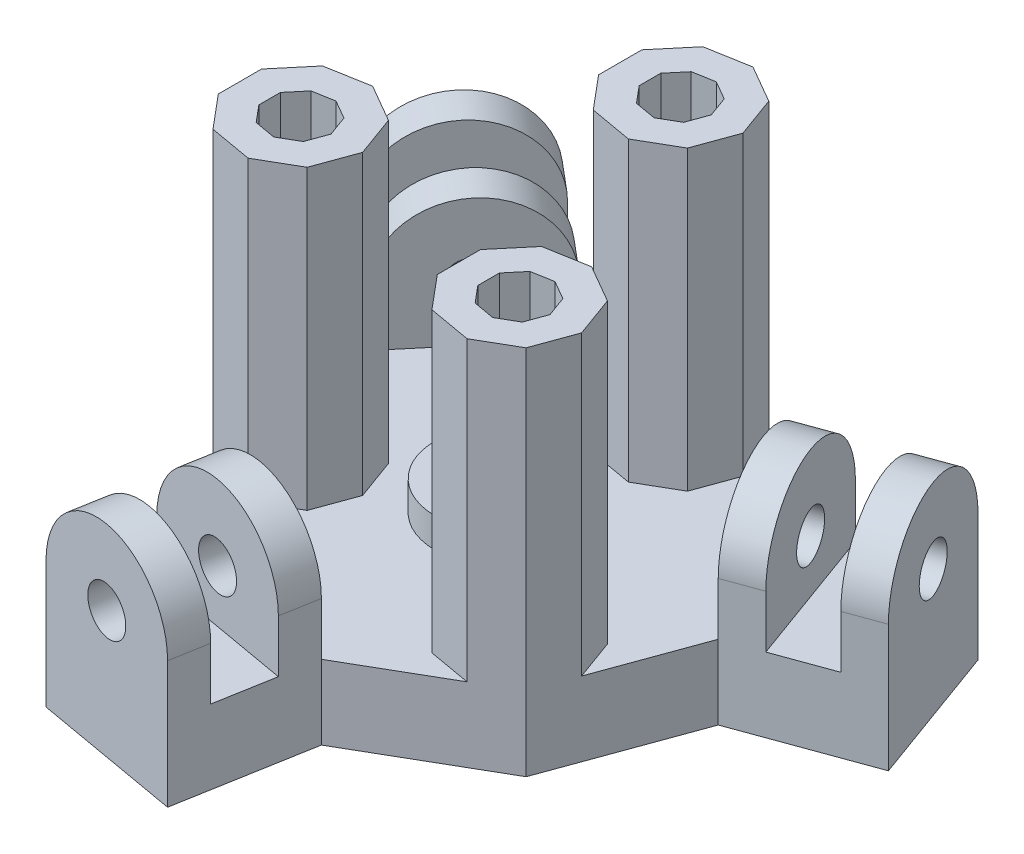
SolidWorks part; units mm, degrees
ref_plane "Front Plane" through (0, 0, 0) normal (0, 0, 1) x (1, 0, 0)
ref_plane "Top Plane" through (0, 0, 0) normal (0, 1, 0) x (1, 0, 0)
ref_plane "Right Plane" through (0, 0, 0) normal (1, 0, 0) x (0, 0, -1)
sketch "Sketch1" plane through (0, 0, 0) normal (0, 1, 0) x (1, 0, 0)
  line L0 (-17.5976, -6.405) -> (-9.3635, -16.2181)
  line L1 (14.3457, -12.0375) -> (18.727, 0)
  line L2 (18.727, 0) -> (14.3457, 12.0375)
  line L3 (14.3457, 12.0375) -> (3.2519, 18.4425)
  line L4 (3.2519, 18.4425) -> (-9.3635, 16.2181)
  line L5 (-9.3635, 16.2181) -> (-17.5976, 6.405)
  line L6 (-17.5976, 6.405) -> (-17.5976, -6.405)
  line L7 (-9.3635, -16.2181) -> (3.2519, -18.4425)
  line L8 (3.2519, -18.4425) -> (14.3457, -12.0375)
  line L9 (14.3457, 12.0375) -> (18.727, 0)
  line L10 (14.3457, 12.0375) -> (25.0112, 15.9194)
  line L11 (18.727, 0) -> (29.3925, 3.8819)
  line L12 (25.0112, 15.9194) -> (29.3925, 3.8819)
  line L13 (3.2519, -18.4425) -> (-9.3635, -16.2181)
  line L14 (3.2519, -18.4425) -> (1.281, -29.6201)
  line L15 (-9.3635, -16.2181) -> (-11.3344, -27.3956)
  line L16 (1.281, -29.6201) -> (-11.3344, -27.3956)
  line L17 (-17.5976, 6.405) -> (-9.3635, 16.2181)
  line L18 (-17.5976, 6.405) -> (-26.2922, 13.7007)
  line L19 (-9.3635, 16.2181) -> (-18.0581, 23.5137)
  line L20 (-26.2922, 13.7007) -> (-18.0581, 23.5137)
  circle A0 centre (0, 0) radius 17.5976 construction
  circle A1 centre (0, 0) radius 4
  dimension "D1" = 35.1953
  dimension "D2" = 8
  dimension "D3" = 11.35
extrude "Boss-Extrude1" add sketch "Sketch1" along normal blind 6.35 contours L16 L14 L7 L15 | L7 L8 L1 L2 L3 L4 L5 L6 L0 A1 | L12 L10 L2 L11 | L20 L18 L5 L19 region at (-17.08, 0, 0) region at (-4.0413, 0, 22.9191) region at (-17.8279, 0, -14.9594) region at (21.8691, 0, -7.9597)
ref_plane "Plane1" through (-5.0267, 0, 28.5079) normal (0.1736, 0, -0.9848) x (-0.9848, 0, -0.1736)
sketch "Sketch4" plane through (-5.0267, 0, 28.5079) normal (0.1736, 0, -0.9848) x (-0.9848, 0, -0.1736)
  line L0 (-6.405, 6.35) -> (-6.405, 10.85)
  line L1 (6.405, 6.35) -> (6.405, 10.85)
  line L2 (-6.405, 6.35) -> (6.405, 6.35)
  arc A0 (6.405, 10.85) -> (-6.405, 10.85) centre (0, 10.85) ccw
  circle A1 centre (0, 10.85) radius 2
  dimension "D2" = 4
  dimension "D1" = 4.5
extrude "Boss-Extrude2" add sketch "Sketch4" along normal blind 3.18
ref_plane "Plane2" through (-3.0558, 0, 17.3303) normal (0.1736, 0, -0.9848) x (-0.9848, 0, -0.1736)
sketch "Sketch6" plane through (-3.0558, 0, 17.3303) normal (0.1736, 0, -0.9848) x (-0.9848, 0, -0.1736)
  line L0 (-6.405, 6.35) -> (-6.405, 10.85)
  line L1 (6.405, 6.35) -> (6.405, 10.85)
  line L2 (-6.405, 6.35) -> (6.405, 6.35)
  arc A0 (6.405, 10.85) -> (-6.405, 10.85) centre (0, 10.85) ccw
  circle A1 centre (0, 10.85) radius 2
  dimension "D2" = 4
  dimension "D1" = 4.5
extrude "Boss-Extrude4" add sketch "Sketch6" against normal blind 3.175
ref_plane "Plane3" through (27.2019, 0, -9.9007) normal (-0.9397, 0, 0.342) x (0.342, 0, 0.9397)
sketch "Sketch8" plane through (27.2019, 0, -9.9007) normal (-0.9397, 0, 0.342) x (0.342, 0, 0.9397)
  line L0 (-6.405, 10.85) -> (-6.405, 6.35)
  line L1 (-6.405, 6.35) -> (6.405, 6.35)
  line L2 (6.405, 6.35) -> (6.405, 10.85)
  arc A0 (6.405, 10.85) -> (-6.405, 10.85) centre (0, 10.85) ccw
  circle A1 centre (0, 10.85) radius 2
  dimension "D2" = 4
  dimension "D1" = 4.5
extrude "Boss-Extrude5" add sketch "Sketch8" along normal blind 3.175
ref_plane "Plane4" through (16.5364, 0, -6.0187) normal (-0.9397, 0, 0.342) x (0.342, 0, 0.9397)
sketch "Sketch9" plane through (16.5364, 0, -6.0187) normal (-0.9397, 0, 0.342) x (0.342, 0, 0.9397)
  line L0 (-6.405, 6.35) -> (-6.405, 10.85)
  line L1 (-6.405, 6.35) -> (6.405, 6.35)
  line L2 (6.405, 6.35) -> (6.405, 10.85)
  arc A0 (-6.405, 10.85) -> (6.405, 10.85) centre (0, 10.85) cw
  circle A1 centre (0, 10.85) radius 2
  dimension "D2" = 4
  dimension "D1" = 4.5
extrude "Boss-Extrude6" add sketch "Sketch9" against normal blind 3.175
ref_plane "Plane5" through (-22.1752, 0, -18.6072) normal (0.766, 0, 0.6428) x (0.6428, 0, -0.766)
sketch "Sketch10" plane through (-22.1752, 0, -18.6072) normal (0.766, 0, 0.6428) x (0.6428, 0, -0.766)
  line L0 (-6.405, 10.85) -> (-6.405, 6.35)
  line L1 (-6.405, 6.35) -> (6.405, 6.35)
  line L2 (6.405, 6.35) -> (6.405, 10.85)
  arc A0 (6.405, 10.85) -> (-6.405, 10.85) centre (0, 10.85) ccw
  circle A1 centre (0, 10.85) radius 2
  dimension "D2" = 4
  dimension "D1" = 4.5
extrude "Boss-Extrude7" add sketch "Sketch10" along normal blind 3.175
ref_plane "Plane6" through (-13.4806, 0, -11.3115) normal (0.766, 0, 0.6428) x (0.6428, 0, -0.766)
sketch "Sketch11" plane through (-13.4806, 0, -11.3115) normal (0.766, 0, 0.6428) x (0.6428, 0, -0.766)
  line L0 (-6.405, 10.85) -> (-6.405, 6.35)
  line L1 (-6.405, 6.35) -> (6.405, 6.35)
  line L2 (6.405, 6.35) -> (6.405, 10.85)
  arc A0 (6.405, 10.85) -> (-6.405, 10.85) centre (0, 10.85) ccw
  circle A1 centre (0, 10.85) radius 2
  dimension "D2" = 4
  dimension "D1" = 4.5
extrude "Boss-Extrude8" add sketch "Sketch11" against normal blind 3.175
ref_plane "Plane7" through (0, 6.35, 0) normal (0, 1, 0) x (1, 0, 0)
sketch "Sketch12" plane through (0, 6.35, 0) normal (0, 1, 0) x (1, 0, 0)
  line L9 (14.3457, -12.0375) -> (18.727, 0) construction
  line L29 (14.3457, -12.0375) -> (15.6105, -8.5626)
  line L38 (15.6105, -8.5626) -> (14.3457, -5.0876)
  line L48 (6.4544, 9.6437) -> (7.7192, 13.1186)
  line L49 (3.2519, 18.4425) -> (-0.3898, 17.8004)
  line L50 (-0.3898, 17.8004) -> (-2.7668, 14.9676)
  line L51 (-2.7668, 14.9676) -> (-2.7668, 11.2696)
  line L52 (-2.7668, 11.2696) -> (-0.3898, 8.4369)
  line L53 (-0.3898, 8.4369) -> (3.2519, 7.7947)
  line L54 (3.2519, 7.7947) -> (6.4544, 9.6437)
  line L55 (7.7192, 13.1186) -> (6.4544, 16.5935)
  line L56 (6.4544, 16.5935) -> (3.2519, 18.4425)
  line L57 (14.3457, -5.0876) -> (11.1432, -3.2387)
  line L58 (11.1432, -3.2387) -> (7.5015, -3.8808)
  line L59 (7.5015, -3.8808) -> (5.1245, -6.7136)
  line L60 (5.1245, -6.7136) -> (5.1245, -10.4115)
  line L61 (5.1245, -10.4115) -> (7.5015, -13.2443)
  line L62 (7.5015, -13.2443) -> (11.1432, -13.8865)
  line L63 (11.1432, -13.8865) -> (14.3457, -12.0375)
  line L64 (-17.5976, -6.405) -> (-9.3635, -16.2181) construction
  line L65 (3.2519, -18.4425) -> (14.3457, -12.0375) construction
  line L66 (-17.5976, -6.405) -> (-15.2206, -9.2378)
  line L67 (-15.2206, -9.2378) -> (-11.5789, -9.8799)
  line L68 (-11.5789, -9.8799) -> (-8.3764, -8.031)
  line L69 (-8.3764, -8.031) -> (-7.1116, -4.556)
  line L70 (-7.1116, -4.556) -> (-8.3764, -1.0811)
  line L71 (-8.3764, -1.0811) -> (-11.5789, 0.7678)
  line L72 (-11.5789, 0.7678) -> (-15.2206, 0.1257)
  line L73 (-15.2206, 0.1257) -> (-17.5976, -2.7071)
  line L74 (-17.5976, -2.7071) -> (-17.5976, -6.405)
  line L75 (14.3457, 12.0375) -> (3.2519, 18.4425) construction
  line L76 (-0.2268, 12.1941) -> (0.9617, 10.7777)
  line L77 (4.3838, 11.3812) -> (5.0162, 13.1186)
  line L78 (5.0162, 13.1186) -> (4.3838, 14.8561)
  line L79 (4.3838, 14.8561) -> (2.7825, 15.7806)
  line L80 (2.7825, 15.7806) -> (0.9617, 15.4595)
  line L81 (0.9617, 15.4595) -> (-0.2268, 14.0431)
  line L82 (-0.2268, 14.0431) -> (-0.2268, 12.1941)
  line L83 (0.9617, 10.7777) -> (2.7825, 10.4567)
  line L84 (2.7825, 10.4567) -> (4.3838, 11.3812)
  line L86 (12.2751, -10.3) -> (12.9075, -8.5626)
  line L87 (12.9075, -8.5626) -> (12.2751, -6.8251)
  line L88 (12.2751, -6.8251) -> (10.6738, -5.9006)
  line L89 (10.6738, -5.9006) -> (8.853, -6.2217)
  line L90 (8.853, -6.2217) -> (7.6645, -7.6381)
  line L91 (7.6645, -7.6381) -> (7.6645, -9.4871)
  line L92 (7.6645, -9.4871) -> (8.853, -10.9034)
  line L93 (8.853, -10.9034) -> (10.6738, -11.2245)
  line L94 (10.6738, -11.2245) -> (12.2751, -10.3)
  line L95 (-10.447, -6.2935) -> (-9.8146, -4.556)
  line L96 (-9.8146, -4.556) -> (-10.447, -2.8186)
  line L97 (-10.447, -2.8186) -> (-12.0483, -1.8941)
  line L98 (-12.0483, -1.8941) -> (-13.8691, -2.2152)
  line L99 (-13.8691, -2.2152) -> (-15.0576, -3.6316)
  line L100 (-15.0576, -3.6316) -> (-15.0576, -5.4805)
  line L101 (-15.0576, -5.4805) -> (-13.8691, -6.8969)
  line L102 (-13.8691, -6.8969) -> (-12.0483, -7.218)
  line L103 (-12.0483, -7.218) -> (-10.447, -6.2935)
  circle A0 centre (2.3132, 13.1186) radius 5.08 construction
  circle A1 centre (10.2045, -8.5626) radius 5.08 construction
  circle A2 centre (-12.5176, -4.556) radius 5.08 construction
  circle A3 centre (2.3132, 13.1186) radius 2.54 construction
  circle A4 centre (10.2045, -8.5626) radius 2.54 construction
  circle A5 centre (-12.5176, -4.556) radius 2.54 construction
  dimension "D1" = 10.16
  dimension "D2" = 2.54
  dimension "D3" = 2.54
  dimension "D4" = 2.54
extrude "Boss-Extrude9" add sketch "Sketch12" along normal blind 25.4
ref_plane "Plane8" through (0, 6.35, 0) normal (0, 1, 0) x (1, 0, 0)
sketch "Sketch15" plane through (0, 6.35, 0) normal (0, 1, 0) x (1, 0, 0)
  circle A0 centre (0, 0) radius 4
  circle A2 centre (0, 0) radius 5.5
  dimension "D1" = 8
  dimension "D2" = 11
extrude "Boss-Extrude10" add sketch "Sketch15" along normal blind 2.54
